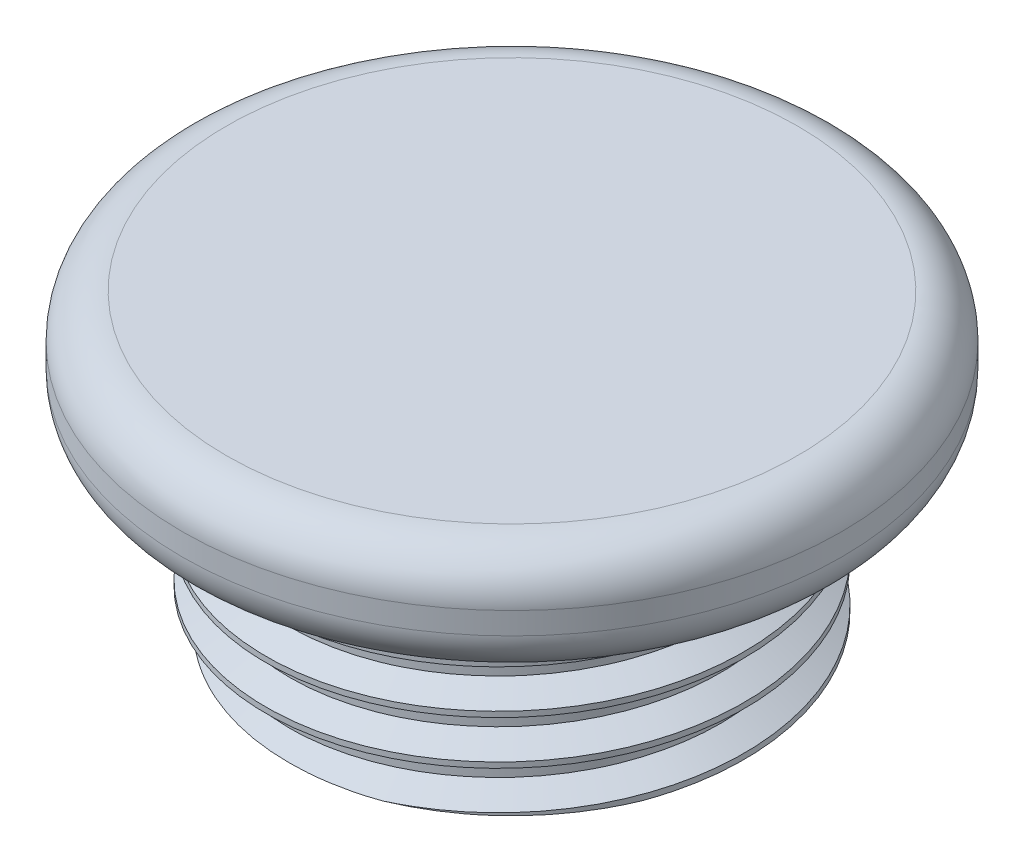
SolidWorks part; units mm, degrees
ref_plane "Front Plane" through (0, 0, 0) normal (0, 0, 1) x (1, 0, 0)
ref_plane "Top Plane" through (0, 0, 0) normal (0, 1, 0) x (1, 0, 0)
ref_plane "Right Plane" through (0, 0, 0) normal (1, 0, 0) x (0, 0, -1)
sketch "Sketch1" plane through (0, 0, 0) normal (0, 1, 0) x (1, 0, 0)
  circle A0 centre (0, 0) radius 4.9
  dimension "D1" = 9.8
extrude "Boss-Extrude1" add sketch "Sketch1" along normal blind 4
thread "Thread1" pitch 1 method extrude trim with end face yes profile "Thread Profile1" start angle 0, offset 0, length 0, pitch 1, diameter 9.8
ref_plane "Plane1" through (-4.9, 4, 0) normal (0, 0, 1) x (-1, 0, 0)
sketch "Thread Profile1" plane through (-4.9, 4, 0) normal (0, 0, 1) x (-1, 0, 0)
  line L0 (0, 0) -> (0, 1) construction
  line L1 (0, 0) -> (0.5413, 0.3125)
  line L2 (0.5413, 0.3125) -> (0.5413, 0.4375)
  line L3 (0.5413, 0.4375) -> (0, 0.75)
  line L4 (0.5413, 0.375) -> (0, 0.375) construction
  line L11 (0, 0) -> (0, 0.75)
  point P2 (0, 0)
  dimension "Pitch" = 1
  dimension "Profile_Angle" = 60
  dimension "Profile_Land" = 0.125
  dimension "Profile_Height" = 0.5413
sketch "Sketch5" plane through (0, 4, 0) normal (0, 1, 0) x (1, 0, 0)
  circle A0 centre (0, 0) radius 7.5
  dimension "D1" = 15
extrude "Boss-Extrude2" add sketch "Sketch5" along normal blind 2.5
fillet "Fillet1" radius 1 2 edges at (0, 4, 7.5) (0, 6.5, 7.5)
